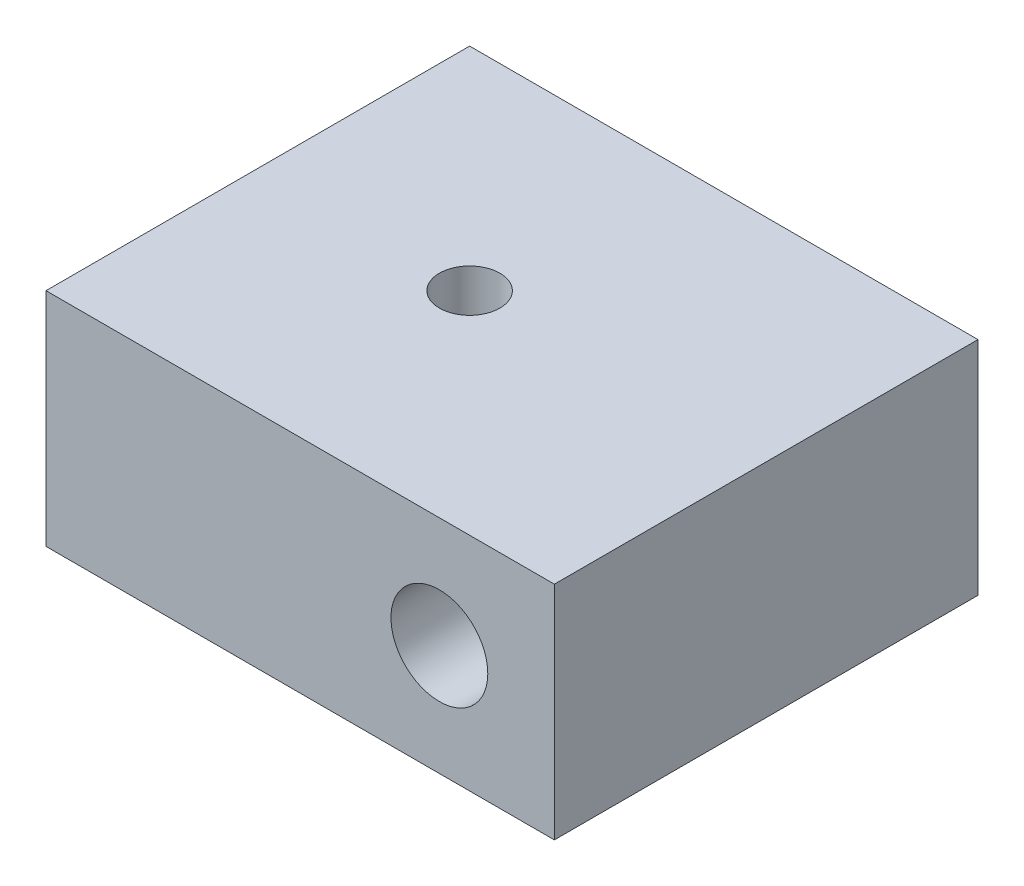
SolidWorks part; units mm, degrees
ref_plane "Front Plane" through (0, 0, 0) normal (0, 0, 1) x (1, 0, 0)
ref_plane "Top Plane" through (0, 0, 0) normal (0, 1, 0) x (1, 0, 0)
ref_plane "Right Plane" through (0, 0, 0) normal (1, 0, 0) x (0, 0, -1)
sketch "Sketch1" plane through (0, 0, 0) normal (0, 1, 0) x (1, 0, 0)
  line L1 (0, 0) -> (42, 0)
  line L2 (0, 0) -> (0, 35)
  line L3 (0, 35) -> (42, 35)
  line L4 (42, 0) -> (42, 35)
  circle A0 centre (17.5, 17.5) radius 2.5
  point P7 (0, 0)
  point P9 (0, 0)
  point P10 (0, 17.5)
  point P11 (26.6759, 0)
  point P12 (43.6161, 35)
  dimension "D2" = 5
  dimension "D1" = 35
  dimension "D3" = 17.5
  dimension "D4" = 42
extrude "Boss-Extrude1" add sketch "Sketch1" along normal blind 18.3
sketch "Sketch2" plane through (0, 0, 0) normal (0, 0, 1) x (1, 0, 0)
  line L1 (17.5, 0) -> (17.5, 18.3) construction
  line L2 (0, 0) -> (42, 0) construction
  line L3 (0, 18.3) -> (42, 18.3) construction
  line L4 (20, 18.3) -> (15, 18.3) construction
  circle A0 centre (32.5, 9.15) radius 4
  point P2 (0, 0)
  dimension "D2" = 8
  dimension "D1" = 15
  dimension "D3" = 9.15
extrude "Cut-Extrude1" cut sketch "Sketch2" against normal through all
equation "\"8mm hole\" = 8mm"
equation "\"22mm hole\"= 22mm"
equation "\"D2@Sketch2\"= \"8mm hole\""
